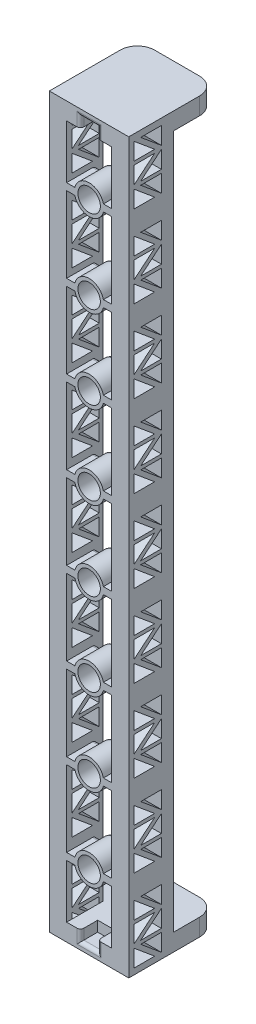
SolidWorks part; units mm, degrees
ref_plane "Front Plane" through (0, 0, 0) normal (0, 0, 1) x (1, 0, 0)
ref_plane "Top Plane" through (0, 0, 0) normal (0, 1, 0) x (1, 0, 0)
ref_plane "Right Plane" through (0, 0, 0) normal (1, 0, 0) x (0, 0, -1)
sketch "Sketch1" plane through (0, 0, 0) normal (0, 0, 1) x (1, 0, 0)
  line L0 (6.5, 100.5) -> (6.5, -100.5)
  line L1 (-11.5, 105.5) -> (11.5, 105.5)
  line L2 (-11.5, 105.5) -> (-11.5, -105.5)
  line L3 (-11.5, -105.5) -> (11.5, -105.5)
  line L4 (11.5, 105.5) -> (11.5, -105.5)
  line L5 (-11.5, 105.5) -> (11.5, -105.5) construction
  line L6 (-11.5, -105.5) -> (11.5, 105.5) construction
  line L7 (-6.5, -100.5) -> (6.5, -100.5)
  line L8 (-6.5, 100.5) -> (-6.5, -100.5)
  line L9 (-6.5, 100.5) -> (6.5, 100.5)
  point P0 (0, 0)
  dimension "D1" = 23
  dimension "D2" = 211
  dimension "D3" = 5
extrude "Boss-Extrude1" add sketch "Sketch1" along normal blind 13
sketch "Sketch7" plane through (0, 0, 13) normal (0, 0, 1) x (1, 0, 0)
  line L0 (0.0237, 87.6593) -> (0.0237, 80.2815) construction
  line L5 (-3.3958, 83) -> (-7.3958, 83)
  line L6 (7.4431, 85) -> (3.4431, 85)
  line L11 (-3.3958, 85) -> (-3.3958, 83)
  line L12 (-7.3958, 85) -> (-3.3958, 85)
  line L13 (3.4431, 85) -> (3.4431, 83)
  line L14 (3.4431, 83) -> (7.4431, 83)
  line L15 (7.4431, 83) -> (7.4431, 85)
  line L16 (-7.3958, 83) -> (-7.3958, 85)
  line L18 (11.5, 105.5) -> (-11.5, 105.5) construction
  circle A0 centre (0.0237, 84) radius 3.25
  circle A1 centre (0.0237, 84) radius 4.25
  point P5 (7.4431, 84)
  dimension "D1" = 6.5
  dimension "D2" = 8.5
  dimension "D3" = 20.5
  dimension "D4" = 4
  dimension "D5" = 2
extrude "Boss-Extrude5" add sketch "Sketch7" against normal blind 8.5
fillet "Fillet4" radius 1 6 edges at (-5.3035, 83, 4.5) (5.3272, 85, 4.5) (-5.3035, 85, 4.5) (0.0237, 88.25, 4.5) (5.3272, 83, 4.5) (0.0237, 79.75, 4.5)
pattern_linear "LPattern7" count 8 spacing 24 along (0, -1, 0) of "Boss-Extrude5", "Fillet4"
sketch "Sketch11" plane through (0, -105.5, 0) normal (0, -1, 0) x (-1, 0, 0)
  line L0 (6.5, -2.0313) -> (6.5, 0)
  line L2 (11.5, 0) -> (-11.5, 0) construction
  line L3 (11.5, -13) -> (11.5, 0) construction
  line L4 (8.5313, 0) -> (6.5, 0)
  line L5 (0, 0) -> (0, -13) construction
  line L6 (11.5, -13) -> (-11.5, -13) construction
  line L7 (-8.5313, 0) -> (-6.5, 0)
  line L8 (-6.5, -2.0313) -> (-6.5, 0)
  arc A0 (6.5, -2.0313) -> (8.5313, 0) centre (6.5, 0) ccw
  arc A1 (-6.5, -2.0313) -> (-8.5313, 0) centre (-6.5, 0) cw
  dimension "D1" = 5
ref_plane "Plane1" through (0, 0, 0) normal (-1, 0, 0) x (0, 0, 1)
ref_plane "Plane2" through (0, 0, 0) normal (0, 1, 0) x (1, 0, 0)
sketch "Sketch15" plane through (0, 105.5, 0) normal (0, 1, 0) x (1, 0, 0)
  line L0 (11.5, 0) -> (-11.5, 0)
  line L4 (11.5, 0) -> (4.4687, 0)
  line L5 (-11.5, 0) -> (-11.5, -13)
  line L6 (-11.5, -13) -> (11.5, -13)
  line L7 (11.5, -13) -> (11.5, 0)
  line L9 (-11.5, 0) -> (-11.5, -13)
  line L10 (-11.5, -13) -> (11.5, -13)
  line L11 (11.5, -13) -> (11.5, 0)
  line L21 (-6.5, 0) -> (-6.5, -2.0313)
  line L25 (-8.5313, 0) -> (-11.5, 0)
  line L26 (6.5, -2.0313) -> (6.5, 0)
  line L27 (6.5, 0) -> (-6.5, 0)
  arc A2 (-8.5313, 0) -> (-6.5, -2.0313) centre (-6.5, 0) ccw
  arc A6 (6.5, -2.0313) -> (4.4687, 0) centre (6.5, 0) ccw
  dimension "D1" = 0
extrude "Boss-Extrude8" add sketch "Sketch15" along normal blind 5
mirror "Mirror5" about plane through (0, 0, 0) normal (0, 1, 0) of "Boss-Extrude8"
sketch "Sketch19" plane through (-11.5, 0, 0) normal (-1, 0, 0) x (0, 0, 1)
  line L0 (13, 105.5) -> (0, 105.5) construction
  line L1 (13, 110.5) -> (13, -110.5) construction
  line L2 (0, 110.5) -> (0, -110.5) construction
  line L3 (0, 110.5) -> (13, 110.5) construction
  line L4 (13, 82.75) -> (0, 82.75) construction
  line L5 (13, 84.75) -> (0, 84.75) construction
  line L6 (0, 98.125) -> (13, 98.125) construction
  line L7 (9.5485, 103.625) -> (3.5485, 103.625)
  line L8 (3.5485, 103.625) -> (3.5485, 98.625)
  line L9 (3.5485, 98.625) -> (9.5485, 103.625)
  line L10 (11.5, 103.625) -> (11.5, 98.625)
  line L11 (11.5, 98.625) -> (5.5, 98.625)
  line L12 (5.5, 98.625) -> (11.5, 103.625)
  line L13 (0, 92.125) -> (13, 92.125) construction
  line L14 (0, 0) -> (13, 0) construction
  line L15 (11.5, 97.625) -> (5.5, 97.625)
  line L16 (11.5, 92.625) -> (11.5, 97.625)
  line L17 (5.5, 97.625) -> (11.5, 92.625)
  line L18 (3.5485, 92.625) -> (3.5485, 97.625)
  line L19 (9.5485, 92.625) -> (3.5485, 92.625)
  line L20 (3.5485, 97.625) -> (9.5485, 92.625)
  line L21 (11.5, 91.625) -> (11.5, 86.625)
  line L22 (5.5, 86.625) -> (11.5, 91.625)
  line L23 (11.5, 86.625) -> (5.5, 86.625)
  line L24 (9.5485, 91.625) -> (3.5485, 91.625)
  line L25 (3.5485, 86.625) -> (9.5485, 91.625)
  line L26 (3.5485, 91.625) -> (3.5485, 86.625)
  dimension "D1" = 5
  dimension "D2" = 5
  dimension "D3" = 2
  dimension "D4" = 1.2493
  dimension "D5" = 1.5
  dimension "D6" = 0.5
  dimension "D7" = 1.875
  dimension "D8" = 6
  dimension "D9" = 0.5
extrude "Cut-Extrude7" cut sketch "Sketch19" against normal blind 5
pattern_linear "LPattern10" count 9 spacing 23.8 along (0, -1, 0) of "Cut-Extrude7"
ref_plane "Plane3" through (0, 0, 0) normal (-1, 0, 0) x (0, 0, 1)
mirror "Mirror7" about plane through (0, 0, 0) normal (-1, 0, 0) of "LPattern10", "Cut-Extrude7"
sketch "Sketch22" plane through (0, 0, 0) normal (0, 0, -1) x (-1, 0, 0)
  line L0 (11.5, 110.5) -> (11.5, -110.5) construction
  line L1 (-11.5, 110.5) -> (11.5, 110.5)
  line L2 (-11.5, 110.5) -> (-11.5, 105.5)
  line L3 (-11.5, 105.5) -> (11.5, 105.5)
  line L4 (11.5, 110.5) -> (11.5, 105.5)
  line L6 (-11.5, -110.5) -> (11.5, -110.5)
  line L7 (-11.5, -110.5) -> (-11.5, -105.5)
  line L8 (-11.5, -105.5) -> (11.5, -105.5)
  line L9 (11.5, -110.5) -> (11.5, -105.5)
  dimension "D1" = 5
  dimension "D2" = 5
extrude "Cut-Extrude9" cut sketch "Sketch22" against normal through all
sketch "Sketch21" plane through (0, 0, 13) normal (0, 0, 1) x (1, 0, 0)
  line L1 (6.5, 100.5) -> (-6.5, 100.5) construction
  line L6 (-4.7323, 0) -> (3.9666, 0) construction
  line L11 (-2.5, 100.5) -> (2.5, 100.5)
  line L12 (-2.5, 100.5) -> (-2.5, 103.5)
  line L13 (-2.5, 103.5) -> (2.5, 103.5)
  line L14 (2.5, 100.5) -> (2.5, 103.5)
  line L15 (11.5, 105.5) -> (-11.5, 105.5) construction
  line L16 (-2.5, -103.5) -> (2.5, -103.5)
  line L17 (2.5, -100.5) -> (2.5, -103.5)
  line L18 (-2.5, -100.5) -> (2.5, -100.5)
  line L19 (-2.5, -100.5) -> (-2.5, -103.5)
  point P18 (0, 105.5)
  point P19 (0, 103.5)
  dimension "D3" = 3
  dimension "D4" = 5
extrude "Cut-Extrude8" cut sketch "Sketch21" against normal blind 5
fillet "Fillet7" radius 1 6 edges at (0, 103.5, 13) (2.5, -102, 13) (0, -103.5, 13) (-2.5, -102, 13) (2.5, 102, 13) (-2.5, 102, 13)
sketch "Sketch23" plane through (0, 0, 0) normal (0, 0, -1) x (-1, 0, 0)
  line L0 (11.5, 105.5) -> (11.5, -105.5) construction
  line L1 (-11.5, 105.5) -> (11.5, 105.5)
  line L2 (-11.5, 105.5) -> (-11.5, 100.5)
  line L3 (-11.5, 100.5) -> (11.5, 100.5)
  line L4 (11.5, 105.5) -> (11.5, 100.5)
  line L5 (-6.5, 100.5) -> (6.5, 100.5) construction
  line L6 (6.5, -100.5) -> (-6.5, -100.5) construction
  line L7 (-11.5, -105.5) -> (11.5, -105.5)
  line L8 (-11.5, -105.5) -> (-11.5, -100.5)
  line L9 (-11.5, -100.5) -> (11.5, -100.5)
  line L10 (11.5, -105.5) -> (11.5, -100.5)
extrude "Boss-Extrude9" add sketch "Sketch23" along normal blind 12.5
fillet "Fillet8" radius 5 4 edges at (11.5, 103, -12.5) (-11.5, 103, -12.5) (-11.5, -103, -12.5) (11.5, -103, -12.5)
sketch "Sketch25" plane through (0, -105.5, 0) normal (0, -1, 0) x (1, 0, 0)
  line L4 (-11.5, 13) -> (-11.5, -7.5) construction
  line L5 (-11.5, 13) -> (11.5, 13) construction
  line L6 (-9, -0.5) -> (-6, -0.5)
  line L7 (-6, -0.5) -> (-6, 2.5)
  line L8 (0, 2.725) -> (0, -1.8067) construction
  line L9 (6, -0.5) -> (6, 2.5)
  line L10 (9, -0.5) -> (6, -0.5)
  arc A0 (-6, 2.5) -> (-9, -0.5) centre (-6, -0.5) ccw
  arc A1 (6, 2.5) -> (9, -0.5) centre (6, -0.5) cw
  dimension "D1" = 13.5
  dimension "D2" = 5.5
  dimension "D3" = 3
extrude "Cut-Extrude11" cut sketch "Sketch25" against normal up to surface (201 mm away) from surface at -5 up to face at (0, 100.5, 4.4807) starting at face at (0, -100.5, 4.7607)
